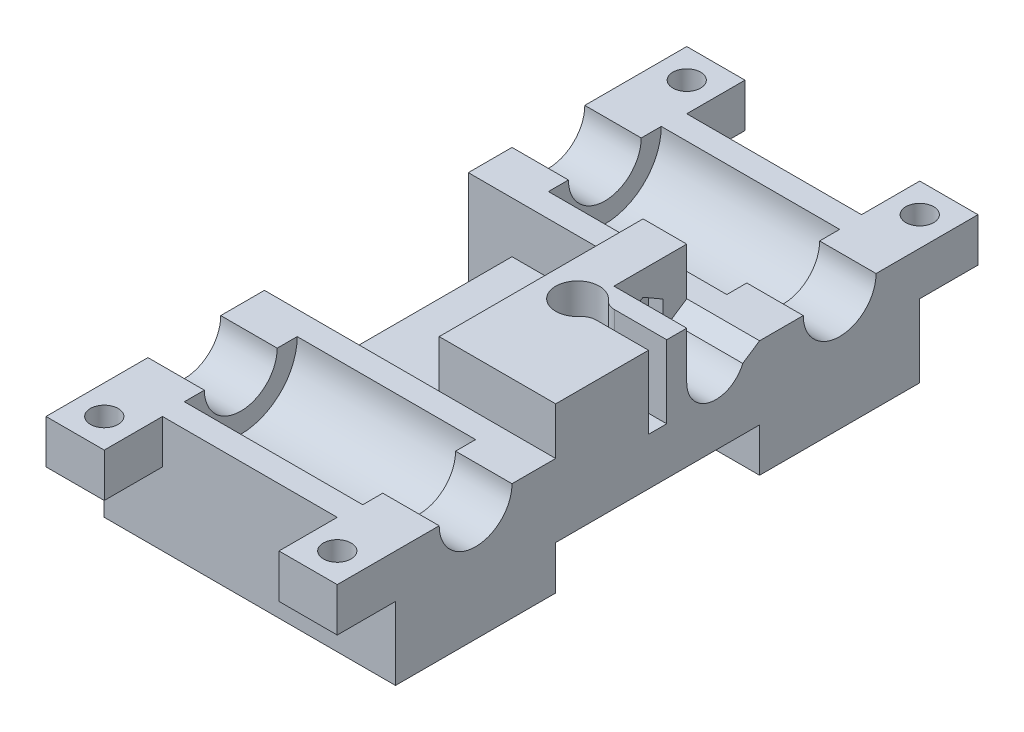
SolidWorks part; units mm, degrees
ref_plane "Front Plane" through (0, 0, 0) normal (0, 0, 1) x (1, 0, 0)
ref_plane "Top Plane" through (0, 0, 0) normal (0, 1, 0) x (1, 0, 0)
ref_plane "Right Plane" through (0, 0, 0) normal (1, 0, 0) x (0, 0, -1)
sketch "Sketch1" plane through (0, 0, 0) normal (0, 1, 0) x (1, 0, 0)
  line L1 (-20, 11) -> (20, 11)
  line L2 (-20, 11) -> (-20, -11)
  line L3 (-20, -11) -> (20, -11)
  line L4 (20, 11) -> (20, -11)
  line L5 (-20, 11) -> (20, -11) construction
  line L6 (-20, -11) -> (20, 11) construction
  point P0 (0, 0)
  dimension "D1" = 40
  dimension "D2" = 22
extrude "Boss-Extrude1" add sketch "Sketch1" along normal blind 11
sketch "Sketch2" plane through (0, 0, 0) normal (0, 1, 0) x (1, 0, 0)
  line L4 (20, -11) -> (20, 11)
  line L5 (-20, -11) -> (20, -11)
  line L6 (-20, 11) -> (-20, -11)
  line L7 (20, 11) -> (-20, 11)
  line L8 (20, -11) -> (20, 11)
  line L9 (-20, -11) -> (20, -11)
  line L10 (-20, 11) -> (-20, -11)
  line L11 (20, 11) -> (-20, 11)
  circle A0 centre (0, 0) radius 7.8438
  dimension "D1" = 0
extrude "Boss-Extrude2" add sketch "Sketch2" against normal blind 5
sketch "Sketch3" plane through (0, 11, 0) normal (0, 1, 0) x (1, 0, 0)
  line L1 (12.25, -7.75) -> (-12.25, -7.75)
  line L2 (12.25, -7.75) -> (12.25, 7.75)
  line L3 (12.25, 7.75) -> (-12.25, 7.75)
  line L4 (-12.25, -7.75) -> (-12.25, 7.75)
  line L5 (12.25, -7.75) -> (-12.25, 7.75) construction
  line L6 (12.25, 7.75) -> (-12.25, -7.75) construction
  point P0 (0, 0)
  dimension "D1" = 15.5
  dimension "D2" = 24.5
extrude "Cut-Extrude1" cut sketch "Sketch3" against normal blind 7.75
fillet "Fillet1" radius 7.75 2 edges at (0, 3.25, 7.75) (0, 3.25, -7.75)
sketch "Sketch4" plane through (-12.25, 0, 0) normal (1, 0, 0) x (0, 0, -1)
  line L0 (7.75, 11) -> (-7.75, 11) construction
  circle A0 centre (0, 11) radius 5
  dimension "D1" = 10
extrude "Cut-Extrude2" cut sketch "Sketch4" against normal through all both and the other way through all
sketch "Sketch5" plane through (0, 11, 0) normal (0, 1, 0) x (1, 0, 0)
  line L1 (20, -11) -> (12, -11)
  line L2 (20, -11) -> (20, -19)
  line L3 (20, -19) -> (12, -19)
  line L4 (12, -11) -> (12, -19)
  circle A0 centre (16, -15) radius 1.9058
  dimension "D1" = 8
  dimension "D2" = 8
  dimension "D3" = 4
  dimension "D4" = 4
extrude "Boss-Extrude3" add sketch "Sketch5" against normal blind 6
sketch "Sketch6" plane through (0, 5, 0) normal (0, -1, 0) x (1, 0, 0)
  line L4 (20, 11) -> (20, 19)
  line L5 (20, 19) -> (12, 19)
  line L6 (12, 19) -> (12, 11)
  line L7 (12, 11) -> (20, 11)
  line L8 (20, 11) -> (20, 19)
  line L9 (20, 19) -> (12, 19)
  line L10 (12, 19) -> (12, 11)
  line L11 (12, 11) -> (20, 11)
  circle A0 centre (16, 15) radius 1.9058 construction
  circle A1 centre (16, 15) radius 1.9058
  circle A2 centre (16, 15) radius 3
  circle M6 centre (16, 15) radius 1.9058
  dimension "D2" = 6
  dimension "D1" = 0
extrude "Cut-Extrude3" cut sketch "Sketch6" against normal blind 3 contours A2 M6
mirror "Mirror8" about plane through (0, 0, 0) normal (1, 0, 0) of "Cut-Extrude3", "Boss-Extrude3"
mirror "Mirror9" [suppressed] about plane through (0, 0, 0) normal (0, 0, 1)
chamfer "Chamfer2" [suppressed] distance 4 angle 45
ref_plane "Plane1" through (0, 0, -25) normal (0, 0, 1) x (1, 0, 0)
sketch "Sketch7" plane through (0, 0, -11) normal (0, 0, -1) x (-1, 0, 0)
  line L0 (-20, 11) -> (-20, -5) construction
  line L1 (-20, 1) -> (-4, 1)
  line L2 (-20, 1) -> (-20, 17.5)
  line L3 (-20, 17.5) -> (-4, 17.5)
  line L4 (-4, 1) -> (-4, 17.5)
  line L5 (-20, 11) -> (20, 11) construction
  dimension "D1" = 16
  dimension "D2" = 16.5
  dimension "D3" = 6.5
extrude "Boss-Extrude5" add sketch "Sketch7" along normal blind 28
mirror "Mirror14" about plane through (0, 0, -25) normal (0, 0, 1) of "Mirror8", "Cut-Extrude3", "Boss-Extrude3", "Cut-Extrude2", "Fillet1", "Cut-Extrude1", "Boss-Extrude2", "Boss-Extrude1"
sketch "Sketch9" plane through (4, 0, 0) normal (-1, 0, 0) x (0, 0, 1)
  line L0 (-39, 1) -> (-39, 11) construction
  line L1 (-11, 1) -> (-39, 1)
  line L2 (-11, 1) -> (-11, 4)
  line L3 (-11, 4) -> (-39, 4)
  line L4 (-39, 1) -> (-39, 4)
  dimension "D1" = 3
extrude "Boss-Extrude6" add sketch "Sketch9" along normal blind 18
sketch "Sketch10" plane through (0, 17.5, 0) normal (0, 1, 0) x (1, 0, 0)
  line L0 (-8.8, 25) -> (8.8, 25) construction
  line L1 (20, 39) -> (20, 11) construction
  line L3 (9, 23.75) -> (20, 23.75)
  line L4 (9, 23.75) -> (9, 26.25)
  line L5 (9, 26.25) -> (20, 26.25)
  line L6 (20, 23.75) -> (20, 26.25)
  circle A0 centre (9, 25) radius 3
  line M4 (20, 11) -> (20, 39)
  dimension "D3" = 6
  dimension "D1" = 0
  dimension "D2" = 11
  dimension "D4" = 2.5
  dimension "D5" = 1.25
extrude "Cut-Extrude4" cut sketch "Sketch10" against normal blind 10 contours L3 A0 L5 L4 | L5 A0 L3 L4 | A0 L3 L5 M4
sketch "Sketch11" plane through (0, 7.5, 0) normal (0, 1, 0) x (1, 0, 0)
  arc A0 (11.7272, 26.25) -> (11.7272, 23.75) centre (9, 25) ccw construction
  arc A1 (11.7272, 26.25) -> (11.7272, 23.75) centre (9, 25) ccw
  circle A2 centre (9, 25) radius 1.75
  point P4 (112.8504, -11.0766)
  dimension "D1" = 3.5
extrude "Cut-Extrude5" cut sketch "Sketch11" against normal through all both and the other way through all contours A2
sketch "Sketch12" plane through (4, 0, 0) normal (-1, 0, 0) x (0, 0, 1)
  line L1 (-39, 4) -> (-39, 11) construction
  circle A0 centre (-33, 11) radius 1.75
  dimension "D3" = 3.5
  dimension "D1" = 0
  dimension "D2" = 6
extrude "Cut-Extrude6" cut sketch "Sketch12" against normal through all both and the other way through all
sketch "Sketch15" plane through (20, 0, 0) normal (1, 0, 0) x (0, 0, -1)
  line L1 (33, 14.1754) -> (30.25, 12.5877)
  line L2 (30.25, 12.5877) -> (30.25, 9.4123)
  line L3 (30.25, 9.4123) -> (33, 7.8246)
  line L4 (33, 7.8246) -> (35.75, 9.4123)
  line L5 (35.75, 9.4123) -> (35.75, 12.5877)
  line L6 (35.75, 12.5877) -> (33, 14.1754)
  circle A0 centre (33, 11) radius 1.75 construction
  circle A1 centre (33, 11) radius 1.75
  circle A2 centre (33, 11) radius 2.75 construction
  dimension "D1" = 5.5
extrude "Cut-Extrude9" cut sketch "Sketch15" against normal blind 12 contours L1 L2 L3 L4 L5 L6
sketch "Sketch16" plane through (20, 0, 0) normal (1, 0, 0) x (0, 0, -1)
  line L1 (29, 11) -> (39, 11)
  line L2 (29, 11) -> (29, 17.5)
  line L3 (29, 17.5) -> (39, 17.5)
  line L4 (39, 11) -> (39, 17.5)
  circle A0 centre (33, 11) radius 1.75 construction
  circle A1 centre (33, 11) radius 1.75
  circle A2 centre (33, 11) radius 4
  dimension "D1" = 8
extrude "Cut-Extrude11" cut sketch "Sketch16" against normal blind 10
chamfer "Chamfer3" distance 2.5 angle 45 1 edges at (15, 11, -37)
fillet "Fillet2" radius 2 2 edges at (11.7272, 12.5, -23.75) (11.7272, 12.5, -26.25)
